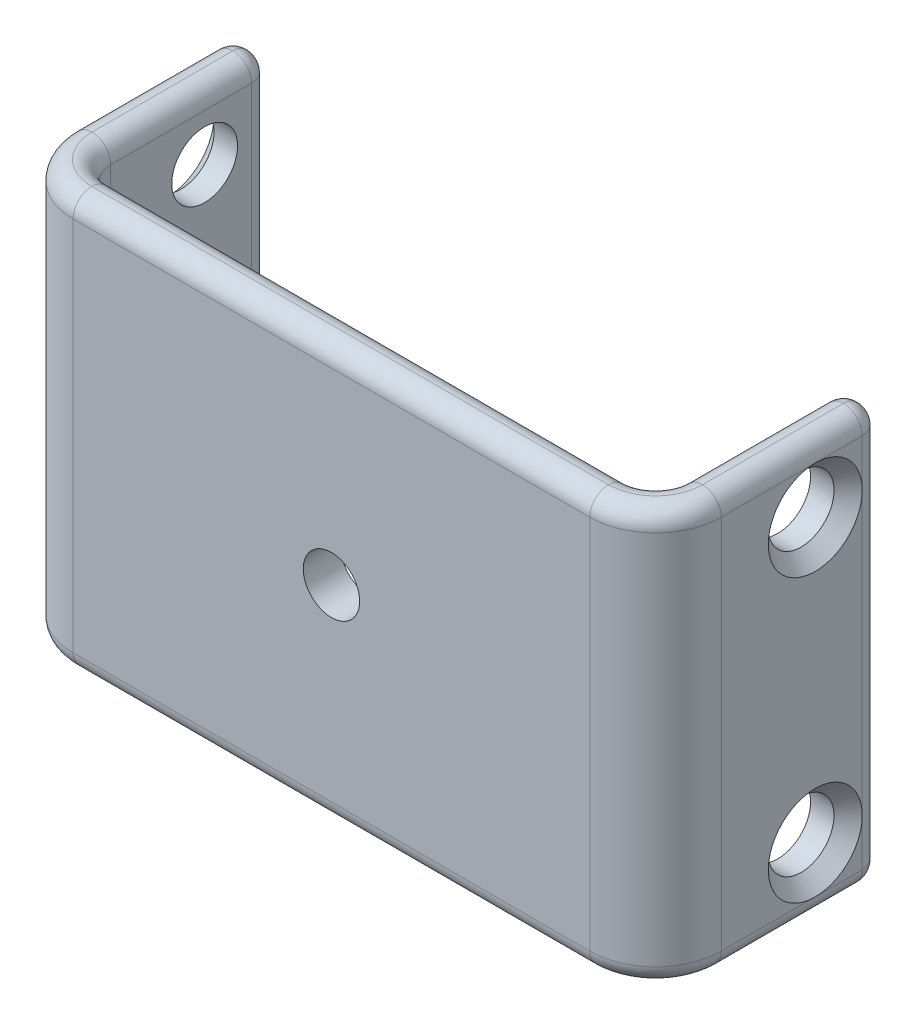
SolidWorks part; units mm, degrees
ref_plane "Front Plane" through (0, 0, 0) normal (0, 0, 1) x (1, 0, 0)
ref_plane "Top Plane" through (0, 0, 0) normal (0, 1, 0) x (1, 0, 0)
ref_plane "Right Plane" through (0, 0, 0) normal (1, 0, 0) x (0, 0, -1)
sketch "Sketch1" plane through (0, 0, 0) normal (0, 1, 0) x (1, 0, 0)
  line L0 (-139.1015, 0) -> (199.6059, 0) construction
  line L1 (-15, 0) -> (-15, -5) construction
  line L2 (0, 71.4158) -> (0, -104.0819) construction
  line L3 (15, 0) -> (15, -5) construction
  line L4 (-13.75, -6.25) -> (13.75, -6.25) construction
  line L5 (-15.25, 0) -> (-15.25, -5)
  line L6 (-13.75, -6.5) -> (13.75, -6.5)
  line L7 (15.25, 0) -> (15.25, -5)
  line L8 (17.25, 0) -> (17.25, -5)
  line L9 (-13.75, -8.5) -> (13.75, -8.5)
  line L10 (-17.25, 0) -> (-17.25, -5)
  line L11 (-17.25, 0) -> (-17.25, 3.5)
  line L12 (17.25, 0) -> (17.25, 3.5)
  line L13 (-17.25, 3.5) -> (-15.25, 3.5)
  line L14 (15.25, 3.5) -> (17.25, 3.5)
  line L15 (-15.25, 3.5) -> (-15.25, 0)
  line L16 (15.25, 3.5) -> (15.25, 0)
  arc A0 (15, -5) -> (13.75, -6.25) centre (13.75, -5) cw construction
  arc A1 (-15, -5) -> (-13.75, -6.25) centre (-13.75, -5) ccw construction
  arc A2 (-15.25, -5) -> (-13.75, -6.5) centre (-13.75, -5) ccw
  arc A3 (15.25, -5) -> (13.75, -6.5) centre (13.75, -5) cw
  arc A4 (17.25, -5) -> (13.75, -8.5) centre (13.75, -5) cw
  arc A5 (-17.25, -5) -> (-13.75, -8.5) centre (-13.75, -5) ccw
  dimension "D2" = 1.25
  dimension "D3" = 1.25
  dimension "D8" = 3.5
  dimension "D1" = 30
  dimension "D4" = 5
  dimension "D10" = 3.5
  dimension "D5" = 0.25
  dimension "D6" = 2
extrude "Boss-Extrude1" add sketch "Sketch1" along normal blind 11 and the other way blind 11
sketch "Sketch2" plane through (0, 0, 0) normal (1, 0, 0) x (0, 0, -1)
  line L0 (0, 45.8672) -> (0, -15.9988) construction
  line L1 (-39.2101, 0) -> (32.5889, 0) construction
  circle A0 centre (0, 7.5) radius 1.75
  circle A1 centre (0, -7.5) radius 1.75
  dimension "D3" = 3.5
  dimension "D4" = 3.5
  dimension "D1" = 7.5
  dimension "D2" = 7.5
extrude "Cut-Extrude1" cut sketch "Sketch2" against normal through all and the other way through all
sketch "Sketch3" plane through (0, 0, 8.5) normal (0, 0, 1) x (1, 0, 0)
  circle A0 centre (0, 0) radius 1.5
  dimension "D1" = 3
extrude "Cut-Extrude2" cut sketch "Sketch3" against normal up to next
fillet "Fillet1" radius 1 24 edges at (-15.25, -11, 0.75) (-17.25, -11, 0.75) (-16.2249, -11, 7.4749) (0, -11, 8.5) (16.2249, -11, 7.4749) (17.25, -11, 0.75) (15.25, -11, 0.75) (14.8107, -11, 6.0607) (0, -11, 6.5) (-14.8107, -11, 6.0607) (-15.25, 0, -3.5) (-17.25, 0, -3.5) (17.25, 0, -3.5) (15.25, 0, -3.5) (0, 11, 6.5) (14.8107, 11, 6.0607) (15.25, 11, 0.75) (17.25, 11, 0.75) (16.2249, 11, 7.4749) (0, 11, 8.5) (-16.2249, 11, 7.4749) (-17.25, 11, 0.75) (-15.25, 11, 0.75) (-14.8107, 11, 6.0607)
chamfer "Chamfer1" distance 0.75 angle 45 4 edges at (17.25, 7.5, -1.75) (17.25, -7.5, -1.75) (-17.25, 7.5, -1.75) (-17.25, -7.5, -1.75)
